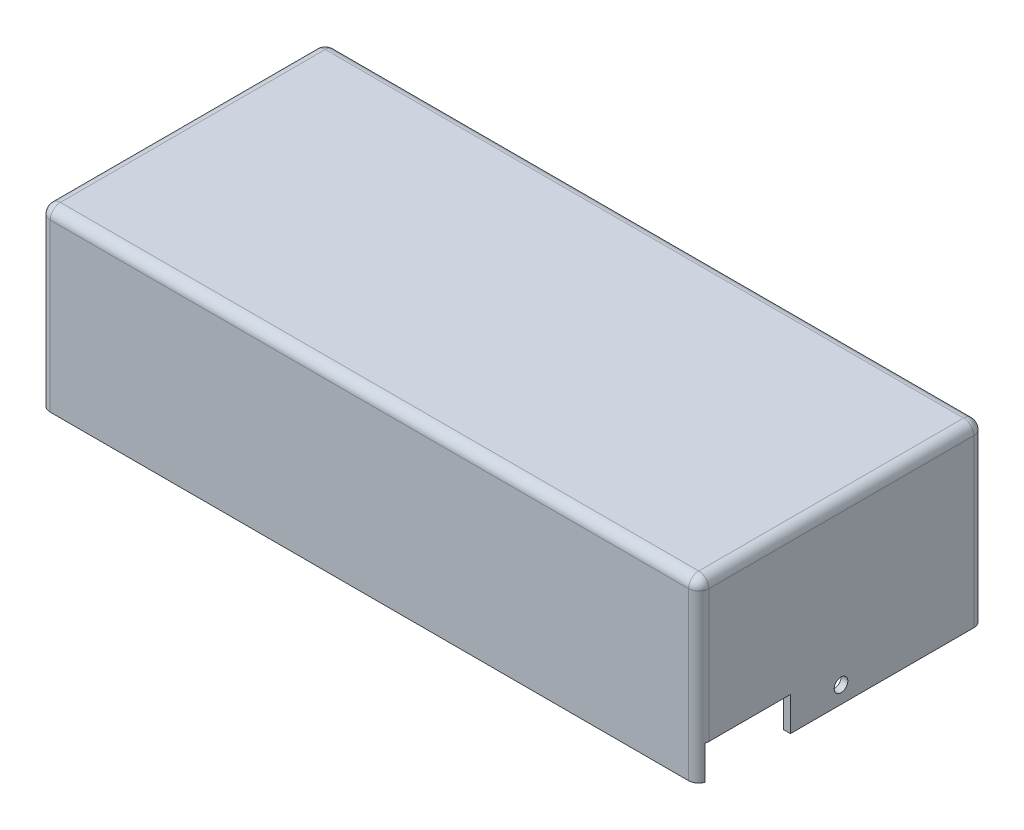
SolidWorks part; units mm, degrees
ref_plane "Front Plane" through (0, 0, 0) normal (0, 0, 1) x (1, 0, 0)
ref_plane "Top Plane" through (0, 0, 0) normal (0, 1, 0) x (1, 0, 0)
ref_plane "Right Plane" through (0, 0, 0) normal (1, 0, 0) x (0, 0, -1)
sketch "Sketch1" plane through (0, 0, 0) normal (0, 0, 1) x (1, 0, 0)
  line L1 (0, 0) -> (194, 0)
  line L2 (0, 0) -> (0, 52)
  line L3 (0, 52) -> (194, 52)
  line L4 (194, 0) -> (194, 52)
  dimension "D1" = 194
  dimension "D2" = 52
extrude "Boss-Extrude1" add sketch "Sketch1" along normal blind 84
sketch "Sketch2" plane through (0, 0, 0) normal (0, -1, 0) x (1, 0, 0)
  line L0 (194, 84) -> (194, 0) construction
  line L1 (192, 2) -> (2, 2)
  line L2 (192, 2) -> (192, 82)
  line L3 (192, 82) -> (2, 82)
  line L4 (2, 2) -> (2, 82)
  line L5 (0, 0) -> (194, 0) construction
  line L6 (0, 84) -> (0, 0) construction
  line L7 (0, 84) -> (194, 84) construction
  dimension "D1" = 2
  dimension "D2" = 2
  dimension "D3" = 2
  dimension "D4" = 2
extrude "Cut-Extrude1" cut sketch "Sketch2" against normal blind 50
fillet "Fillet1" radius 1 3 edges at (97, 50, 2) (2, 25, 2) (2, 50, 42)
fillet "Fillet2" radius 1 3 edges at (97.5, 50, 82) (2.2929, 49.7071, 82) (2, 24.5, 82)
fillet "Fillet3" radius 1 5 edges at (192, 24.5, 2) (192, 49.7071, 2.2929) (192, 50, 42) (192, 49.7071, 81.7071) (192, 24.5, 82)
fillet "Fillet4" radius 3 4 edges at (194, 52, 42) (194, 26, 84) (0, 26, 84) (97, 52, 84)
fillet "Fillet5" radius 3 6 edges at (193.1213, 51.1213, 0) (0.8787, 51.1213, 83.1213) (194, 24.5, 0) (95.5, 52, 0) (0, 26, 0) (0, 52, 40.5)
sketch "Sketch3" plane through (194, 0, 0) normal (1, 0, 0) x (0, 0, -1)
  line L0 (-81, 0) -> (-3, 0) construction
  line L1 (-57, 0) -> (-82, 0)
  line L2 (-57, 0) -> (-57, 10)
  line L3 (-57, 10) -> (-82, 10)
  line L4 (-82, 0) -> (-82, 10)
  line L5 (-84, 0) -> (-84, 49) construction
  dimension "D1" = 2
  dimension "D2" = 25
  dimension "D3" = 10
extrude "Cut-Extrude2" cut sketch "Sketch3" against normal blind 5
hole_wizard "Ø4.0mm Dowel Hole1" positions "3DSketch1" profile "Sketch4" hole size "Ø4.0" standard "ISO"
sketch3d "3DSketch1"
  line L0 (194, 0, 57) -> (194, 0, 3) construction
  line L1 (191, 0, 84) -> (191, 49, 84) construction
  point P0 (194, 5, 42.1073)
  dimension "D1" = 5
  dimension "D2" = 42
sketch "Sketch4" plane through (194, 5, 42.1073) normal (0, 1, 0) x (0, 0, -1)
  line L0 (0, 0) -> (0, 21.2017)
  line L1 (0, 21.2017) -> (2, 20)
  line L2 (2, 20) -> (2, 0)
  line L5 (2, 0) -> (0, 0)
  line L10 (0, 21.2017) -> (-2, 20) construction
  line L11 (0, -6.35) -> (0, 107.95) construction
  dimension "Hole Dia." = 4
  dimension "Hole Depth" = 20
  dimension "Drill Angle" = 118
hole_wizard "Ø4.0mm Dowel Hole2" positions "3DSketch2" profile "Sketch5" hole size "Ø4.0" standard "ISO"
sketch3d "3DSketch2"
  line L0 (0, 0, 81) -> (0, 0, 3) construction
  line L1 (3, 0, 0) -> (3, 49, 0) construction
  point P0 (0, 5, 41.8927)
  dimension "D1" = 5
  dimension "D2" = 42
sketch "Sketch5" plane through (0, 5, 41.8927) normal (0, 1, 0) x (0, 0, 1)
  line L0 (0, 0) -> (0, 21.2017)
  line L1 (0, 21.2017) -> (2, 20)
  line L2 (2, 20) -> (2, 0)
  line L5 (2, 0) -> (0, 0)
  line L10 (0, 21.2017) -> (-2, 20) construction
  line L11 (0, -6.35) -> (0, 107.95) construction
  dimension "Hole Dia." = 4
  dimension "Hole Depth" = 20
  dimension "Drill Angle" = 118
